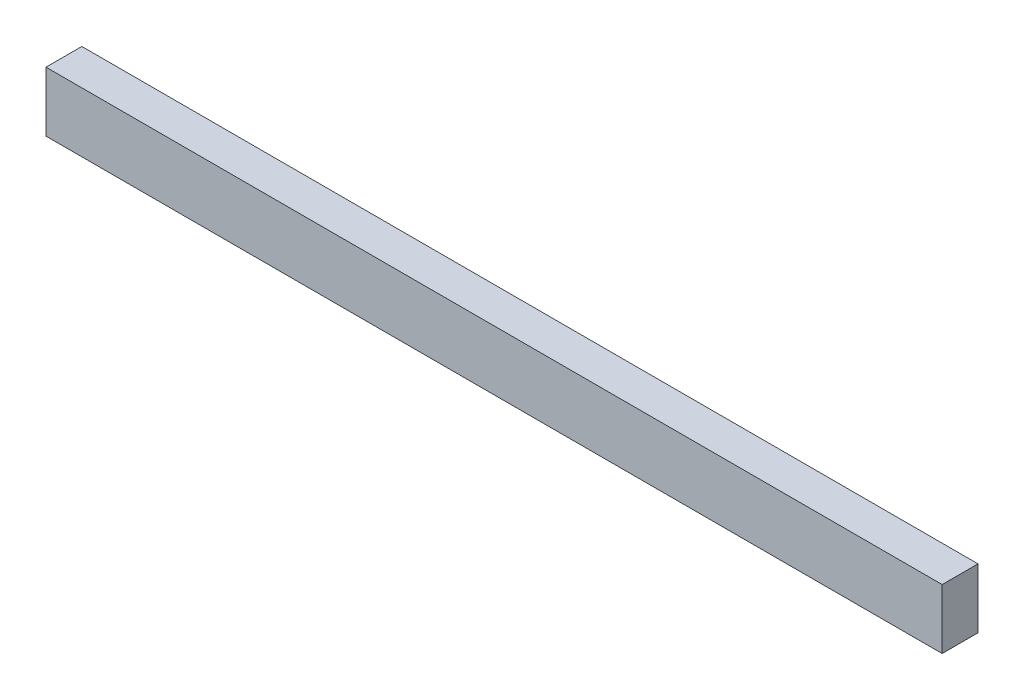
SolidWorks part; units mm, degrees
ref_plane "Front Plane" through (0, 0, 0) normal (0, 0, 1) x (1, 0, 0)
ref_plane "Top Plane" through (0, 0, 0) normal (0, 1, 0) x (1, 0, 0)
ref_plane "Right Plane" through (0, 0, 0) normal (1, 0, 0) x (0, 0, -1)
sketch "Sketch1" plane through (0, 0, 0) normal (0, 0, 1) x (1, 0, 0)
  line L1 (0, 0) -> (150, 0)
  line L2 (0, 0) -> (0, 10)
  line L3 (0, 10) -> (150, 10)
  line L4 (150, 0) -> (150, 10)
  dimension "D1" = 10
  dimension "D2" = 150
extrude "Boss-Extrude1" add sketch "Sketch1" along normal blind 6
